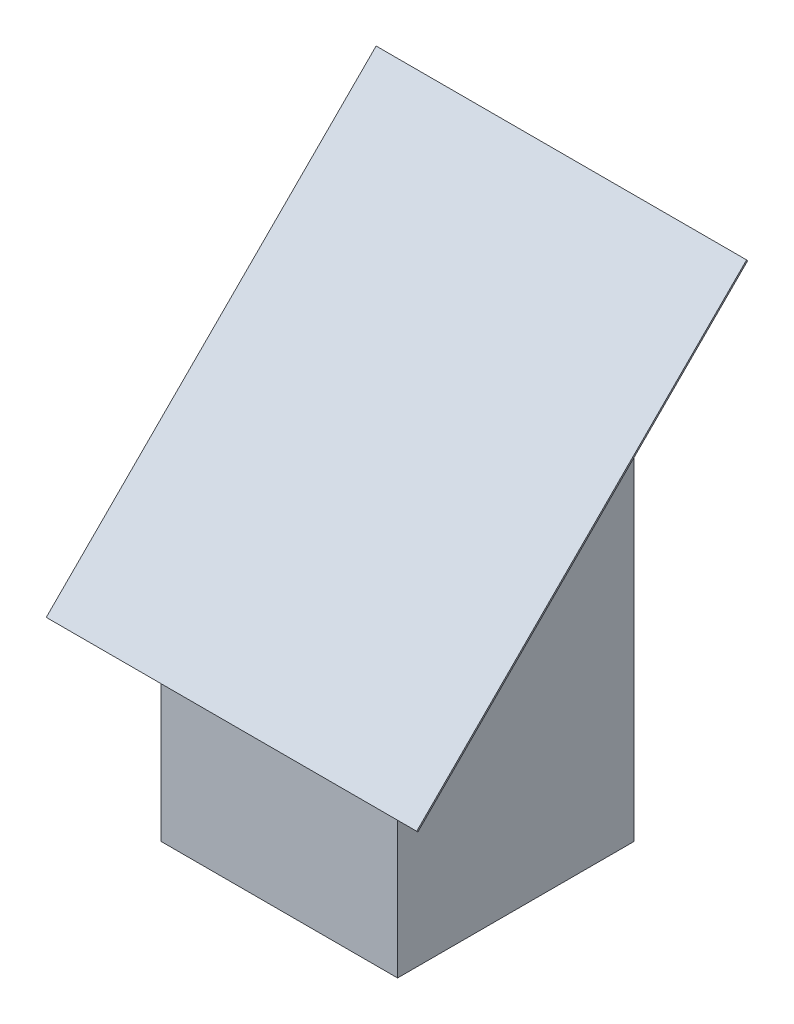
SolidWorks part; units mm, degrees
material "AISI 304"
ref_plane "Front" through (0, 0, 0) normal (0, 0, 1) x (1, 0, 0)
ref_plane "Top" through (0, 0, 0) normal (0, 1, 0) x (1, 0, 0)
ref_plane "Right" through (0, 0, 0) normal (1, 0, 0) x (0, 0, -1)
sketch "Croquis1" plane through (0, 0, 0) normal (0, 1, 0) x (1, 0, 0)
  line L0 (-0.6, -0.6) -> (85.6, -0.6)
  line L1 (0, 0) -> (85, 0)
  line L2 (0, 0) -> (0, 85)
  line L3 (0, 85) -> (85, 85)
  line L4 (85, 0) -> (85, 85)
  line L5 (0, 0) -> (85, 85) construction
  line L6 (0, 85) -> (85, 0) construction
  line L7 (85.6, -0.6) -> (85.6, 85.6)
  line L8 (-0.6, 85.6) -> (85.6, 85.6)
  line L9 (-0.6, -0.6) -> (-0.6, 85.6)
  point P5 (42.5, 42.5)
  dimension "D1" = 85
  dimension "D2" = 0.6
extrude "Saliente-Extruir1" add sketch "Croquis1" along normal blind 170
sketch "Croquis2" plane through (85.6, 0, 0) normal (1, 0, 0) x (0, 0, -1)
  line L0 (85.6, 170) -> (-0.6, 83.8)
  line L1 (-0.6, 170) -> (-0.6, 0) construction
  line L2 (-0.6, 83.8) -> (-0.6, 170)
  line L3 (-0.6, 170) -> (85.6, 170)
  dimension "D1" = 45
extrude "Cortar-Extruir1" cut sketch "Croquis2" against normal through all
sketch "Croquis3" plane through (0, 42.2, 42.2) normal (0, 0.7071, 0.7071) x (1, 0, 0)
  line L1 (-25, 204.7839) -> (110, 204.7839)
  line L2 (-25, 204.7839) -> (-25, 34.7839)
  line L3 (-25, 34.7839) -> (110, 34.7839)
  line L4 (110, 204.7839) -> (110, 34.7839)
  line L5 (-25, 204.7839) -> (110, 34.7839) construction
  line L6 (-25, 34.7839) -> (110, 204.7839) construction
  point P0 (42.5, 119.7839)
extrude "Saliente-Extruir2" add sketch "Croquis3" along normal blind 0.6
